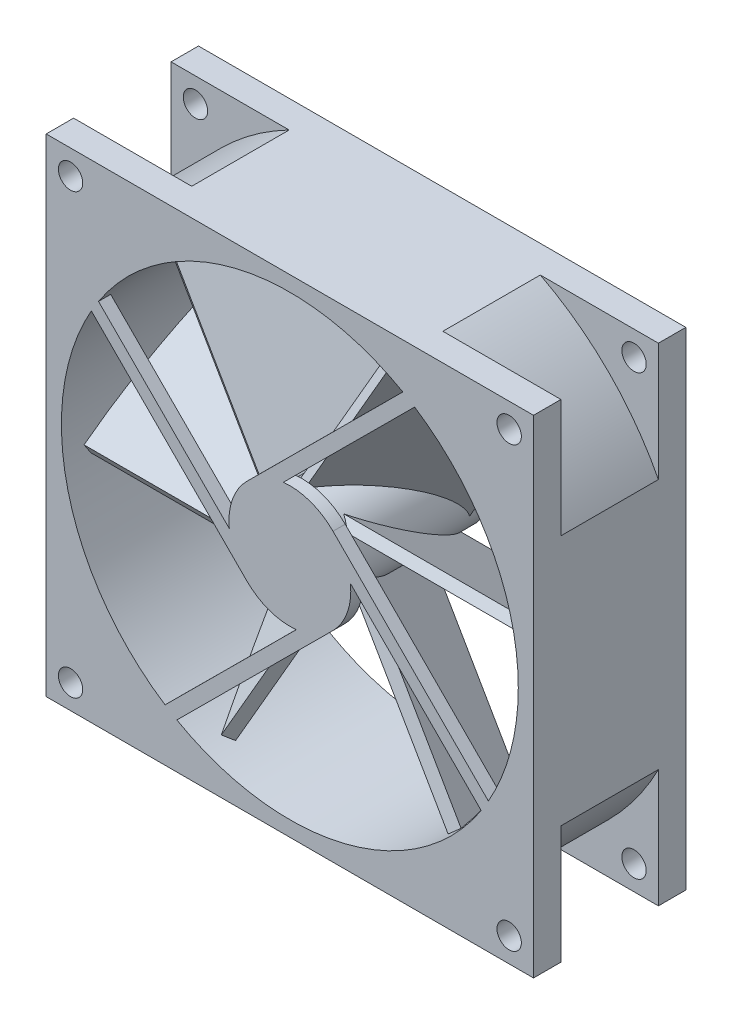
SolidWorks part; units mm, degrees
ref_plane "Ön Düzlem" through (0, 0, 0) normal (0, 0, 1) x (1, 0, 0)
ref_plane "Üst Düzlem" through (0, 0, 0) normal (0, 1, 0) x (1, 0, 0)
ref_plane "Sağ Düzlem" through (0, 0, 0) normal (1, 0, 0) x (0, 0, -1)
sketch "Sketch1" plane through (0, 0, 0) normal (0, 0, 1) x (1, 0, 0)
  line L1 (-40, -40) -> (40, -40)
  line L2 (-40, -40) -> (-40, 40)
  line L3 (-40, 40) -> (40, 40)
  line L4 (40, -40) -> (40, 40)
  line L5 (-40, -40) -> (40, 40) construction
  line L6 (-40, 40) -> (40, -40) construction
  circle A0 centre (0, 0) radius 37.5
  point P0 (0, 0)
  dimension "D3" = 75
  dimension "D1" = 80
  dimension "D2" = 80
extrude "Boss-Extrude1" add sketch "Sketch1" along normal blind 12.5 and the other way blind 12.5
sketch "Sketch2" plane through (0, 0, 0) normal (0, 0, 1) x (1, 0, 0)
  circle A0 centre (0, 0) radius 45
  circle A1 centre (0, 0) radius 60
  dimension "D1" = 90
  dimension "D2" = 120
extrude "Cut-Extrude1" cut sketch "Sketch2" against normal blind 8 and the other way blind 8
sketch "Sketch3" plane through (0, 0, 12.5) normal (0, 0, 1) x (1, 0, 0)
  line L0 (40, 40) -> (-40, 40) construction
  line L1 (-40, 40) -> (-40, -40) construction
  circle A0 centre (-36, 36) radius 2
  circle A1 centre (36, 36) radius 2
  circle A2 centre (36, -36) radius 2
  circle A3 centre (-36, -36) radius 2
  point P15 (0, 0)
  dimension "D1" = 4
  dimension "D2" = 4
  dimension "D3" = 4
  dimension "D4" = 4
extrude "Cut-Extrude2" cut sketch "Sketch3" against normal through all
sketch "Sketch4" plane through (0, 0, 12.5) normal (0, 0, 1) x (1, 0, 0)
  line L0 (-7.0571, 7.085) -> (18.5496, 32.5908)
  line L1 (-1.0675, 9.9429) -> (20.485, 31.4104)
  line L2 (7.085, 7.0571) -> (32.5908, -18.5496)
  line L3 (9.9429, 1.0675) -> (31.4104, -20.485)
  line L4 (7.0571, -7.085) -> (-18.5496, -32.5908)
  line L5 (1.0675, -9.9429) -> (-20.485, -31.4104)
  line L6 (-7.085, -7.0571) -> (-32.5908, 18.5496)
  line L7 (-9.9429, -1.0675) -> (-31.4104, 20.485)
  circle A0 centre (0, 0) radius 10
  circle A1 centre (0, 0) radius 37.5 construction
  point P24 (0, 0)
  circle M12 centre (0, 0) radius 37.5
  dimension "D1" = 20
  dimension "D2" = 4
extrude "Boss-Extrude2" add sketch "Sketch4" against normal blind 2 contours A0 L1 L0 M12 | A0 | A0 L7 L6 M12 | A0 L3 L2 M12 | A0 L5 L4 M12 region at (8.0964, 20.6601, 12.5) region at (0, 0, 12.5) region at (-20.6601, 8.0964, 12.5) region at (20.6601, -8.0964, 12.5) region at (-8.0964, -20.6601, 12.5)
sketch "Sketch5" plane through (0, 0, 10.5) normal (0, 0, -1) x (-1, 0, 0)
  circle A0 centre (0, 0) radius 7.5
  dimension "D1" = 15
extrude "Boss-Extrude3" add sketch "Sketch5" along normal up to surface (23 mm away) up to face at (-34, -36, -12.5)
ref_plane "Plane1" through (20, 0, 0) normal (1, 0, 0) x (0, 0, -1)
sketch "Sketch7" plane through (20, 0, 0) normal (1, 0, 0) x (0, 0, -1)
  line L0 (9.7303, -7.2121) -> (-9.063, 4.5337)
  line L1 (-9.063, 4.5337) -> (-8.1241, 6.036)
  line L2 (-8.1241, 6.036) -> (10.6692, -5.7098)
  line L3 (10.6692, -5.7098) -> (9.7303, -7.2121)
extrude "Boss-Extrude9" add sketch "Sketch7" along normal up to surface and the other way up to surface up to face at (37.5, 0, -12.5) other way up to face at (7.5, 0, 10.5)
pattern_circular "CirPattern1" count 6 over 360 about axis through (0, 0, -33.7132) along (0, 0, 1) of "Boss-Extrude9" reverse direction yes
